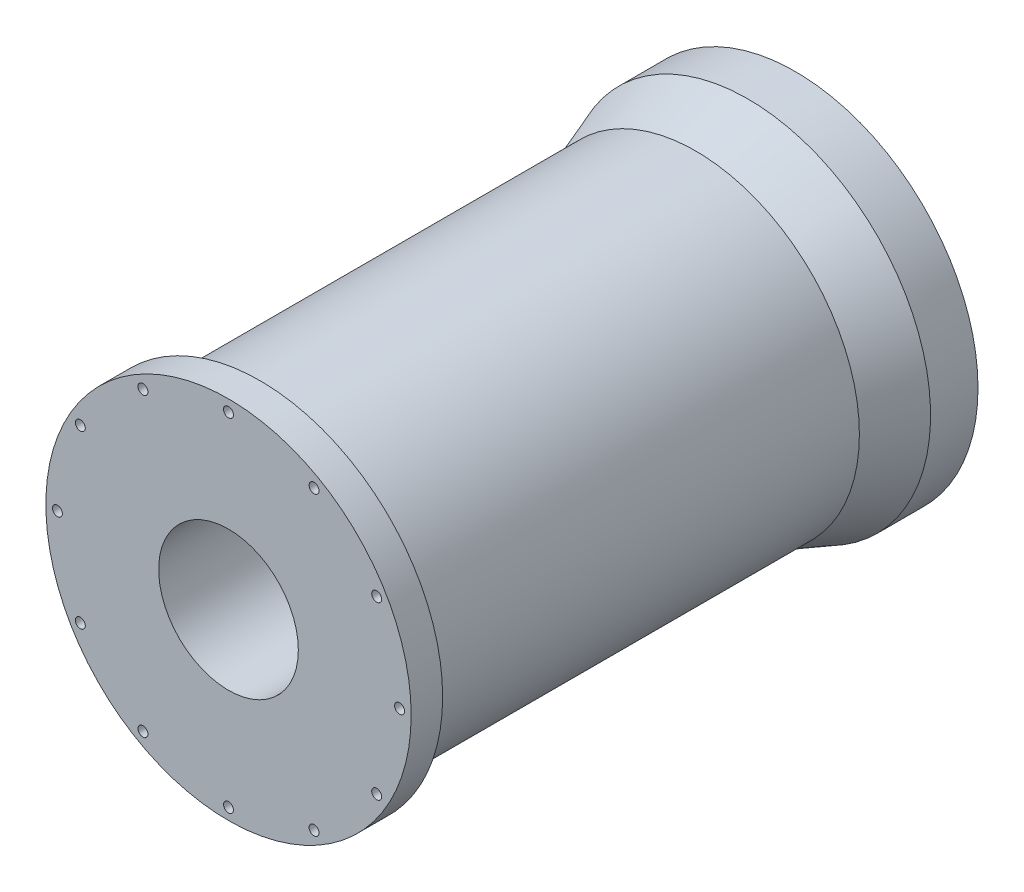
SolidWorks part; units mm, degrees
material "1060 Alloy"
ref_plane "Front Plane" through (0, 0, 0) normal (0, 0, 1) x (1, 0, 0)
ref_plane "Top Plane" through (0, 0, 0) normal (0, 1, 0) x (1, 0, 0)
ref_plane "Right Plane" through (0, 0, 0) normal (1, 0, 0) x (0, 0, -1)
sketch "Sketch2" plane through (0, 0, 0) normal (0, 0, 1) x (1, 0, 0)
  circle A0 centre (0, 0) radius 73.66
extrude "Boss-Extrude1" add sketch "Sketch2" along normal blind 12.7
sketch "Sketch3" plane through (0, 0, 12.7) normal (0, 0, 1) x (1, 0, 0)
  circle A0 centre (0, 0) radius 66
extrude "Boss-Extrude2" add sketch "Sketch3" along normal blind 203.2
sketch "Sketch4" plane through (0, 0, 215.9) normal (0, 0, 1) x (1, 0, 0)
  circle A0 centre (0, 0) radius 73.66
extrude "Boss-Extrude3" add sketch "Sketch4" along normal blind 12.7
sketch "Sketch6" plane through (0, 0, 228.6) normal (0, 0, 1) x (1, 0, 0)
  line L0 (0, -81.026) -> (0, 81.026) construction
  circle A0 centre (0, 69) radius 2
  circle A1 centre (34.5, 59.7558) radius 2
  circle A2 centre (59.7558, 34.5) radius 2
  circle A3 centre (69, 0) radius 2
  circle A4 centre (59.7558, -34.5) radius 2
  circle A5 centre (34.5, -59.7558) radius 2
  circle A6 centre (0, -69) radius 2
  circle A7 centre (-34.5, -59.7558) radius 2
  circle A8 centre (-59.7558, -34.5) radius 2
  circle A9 centre (-69, 0) radius 2
  circle A10 centre (-59.7558, 34.5) radius 2
  circle A11 centre (-34.5, 59.7558) radius 2
  dimension "D1" = 12
extrude "Cut-Extrude1" cut sketch "Sketch6" against normal blind 12.7
chamfer "Chamfer1" distance 10 angle 70 1 edges at (66, 0, 12.7) first distance on face at (66, 0, 12.7)
sketch "Sketch8" plane through (0, 0, 228.6) normal (0, 0, 1) x (1, 0, 0)
  circle A0 centre (0, 0) radius 28.1626
extrude "Cut-Extrude2" cut sketch "Sketch8" against normal blind 150
